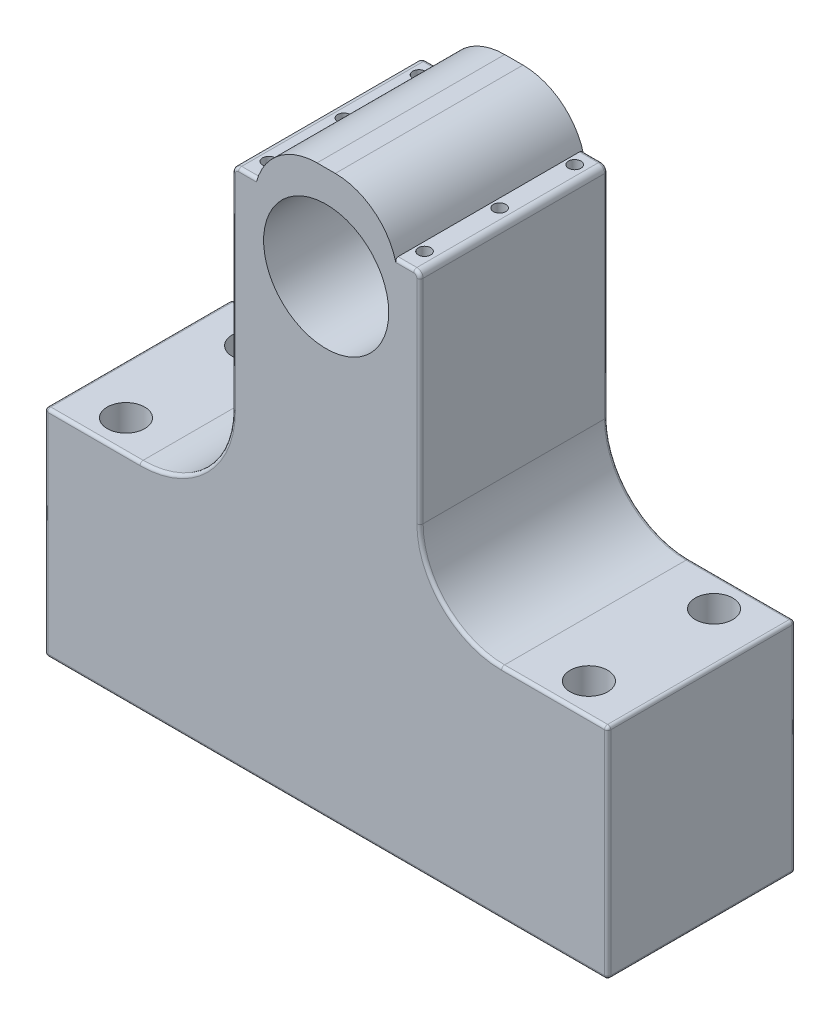
SolidWorks part; units mm, degrees
ref_plane "Plan de face" through (0, 0, 0) normal (0, 0, 1) x (1, 0, 0)
ref_plane "Plan de dessus" through (0, 0, 0) normal (0, 1, 0) x (1, 0, 0)
ref_plane "Plan de droite" through (0, 0, 0) normal (1, 0, 0) x (0, 0, -1)
sketch "Esquisse1" plane through (0, 0, 0) normal (0, 0, 1) x (1, 0, 0)
  line L0 (0, 0) -> (900, 0)
  line L1 (900, 0) -> (900, 150)
  line L3 (0, 144.3329) -> (0, 0)
  line L4 (300, 374.9177) -> (300, 630)
  line L5 (340, 700) -> (560, 700)
  line L6 (600, 630) -> (600, 375)
  line L7 (0, 144.3329) -> (152.4789, 144.3329)
  line L8 (300, 291.854) -> (300, 374.9177)
  line L9 (900, 150) -> (730.278, 150)
  line L10 (600, 375) -> (600, 280.278)
  line L11 (560, 700) -> (560, 630)
  line L12 (560, 630) -> (600, 630)
  line L16 (300, 630) -> (340, 630)
  line L17 (340, 700) -> (340, 630)
  circle A2 centre (450, 550) radius 100
  arc A3 (152.4789, 144.3329) -> (300, 291.854) centre (152.4789, 291.854) ccw
  arc A4 (730.278, 150) -> (600, 280.278) centre (730.278, 280.278) cw
  point P6 (320, 630)
  dimension "D1" = 200
  dimension "D2" = 550
  dimension "D3" = 40
  dimension "D4" = 700
  dimension "D5" = 40
  dimension "D6" = 300
  dimension "D7" = 900
  dimension "D8" = 450
  dimension "D9" = 70
  dimension "D10" = 70
extrude "Boss.-Extru.1" add sketch "Esquisse1" against normal blind 300
sketch "Esquisse2" plane through (0, 144.3329, 0) normal (0, 1, 0) x (1, 0, 0)
  line L0 (152.4789, 300) -> (0, 300) construction
  line L1 (152.4789, 0) -> (0, 0) construction
  line L2 (0, 300) -> (0, 0) construction
  circle A0 centre (80, 250) radius 30
  circle A1 centre (80, 50) radius 30
  dimension "D1" = 60
  dimension "D2" = 60
  dimension "D3" = 50
  dimension "D4" = 50
  dimension "D5" = 80
  dimension "D6" = 80
extrude "Enlèv. mat.-Extru.1" cut sketch "Esquisse2" against normal blind 500
fillet "Congé3" radius 100 2 edges at (340, 700, -150) (560, 700, -150)
fillet "Congé4" radius 10 2 edges at (300, 630, -150) (600, 630, -150)
sketch "Esquisse3" plane through (0, 150, 0) normal (0, 1, 0) x (1, 0, 0)
  line L0 (900, 300) -> (730.278, 300) construction
  line L1 (900, 0) -> (730.278, 0) construction
  line L2 (900, 300) -> (900, 0) construction
  circle A0 centre (820, 250) radius 30
  circle A1 centre (820, 50) radius 30
  dimension "D1" = 60
  dimension "D2" = 60
  dimension "D3" = 50
  dimension "D4" = 50
  dimension "D5" = 80
  dimension "D6" = 80
extrude "Enlèv. mat.-Extru.2" cut sketch "Esquisse3" against normal blind 500
sketch "Esquisse4" plane through (0, 630, 0) normal (0, 1, 0) x (1, 0, 0)
  circle A0 centre (573.7843, 273.4522) radius 10
  circle A1 centre (324.8854, 273.4522) radius 10
  dimension "D1" = 20
  dimension "D2" = 20
extrude "Enlèv. mat.-Extru.3" cut sketch "Esquisse4" against normal blind 100
pattern_linear "Répétition linéaire1" count 3 spacing 120 along (0, 0, 1) of "Enlèv. mat.-Extru.3"
sketch "Esquisse6" plane through (0, 0, 0) normal (0, 0, 1) x (1, 0, 0)
  line L0 (0, 0) -> (0, -200)
  line L1 (0, -200) -> (900, -200)
  line L2 (900, -200) -> (900, 0)
  line L3 (0, 0) -> (900, 0) construction
  line L4 (0, 0) -> (900, 0)
  point P3 (900, -140.103)
  dimension "D1" = 200
extrude "Boss.-Extru.2" add sketch "Esquisse6" against normal blind 300
sketch "Esquisse7" plane through (0, 0, 0) normal (0, 1, 0) x (1, 0, 0)
  circle A0 centre (80.6625, 253.0556) radius 33.1266
  circle A1 centre (80, 50) radius 30
  circle A2 centre (816.2966, 50) radius 26.2966
  circle A3 centre (820, 250) radius 30
extrude "Enlèv. mat.-Extru.4" cut sketch "Esquisse7" against normal blind 300
fillet "Congé6" radius 5 30 edges at (815.139, 150, 0) (575, 630, 0) (597.0711, 627.0711, 0) (600, 450.139, 0) (815.139, 150, -300) (575, 630, -300) (597.0711, 627.0711, -300) (600, 450.139, -300) (325, 630, -300) (302.9289, 627.0711, -300) (300, 455.927, -300) (256.7921, 187.5409, -300) (325, 630, 0) (302.9289, 627.0711, 0) (76.2395, 144.3329, 0) (256.7921, 187.5409, 0) (900, -200, -150) (450, -200, -300) (0, -200, -150) (450, -200, 0) (638.1576, 188.1576, 0) (900, 150, -150) (900, -25, 0) (900, -25, -300) (638.1576, 188.1576, -300) (76.2395, 144.3329, -300) (0, -27.8335, -300) (0, 144.3329, -150) (0, -27.8335, 0) (300, 455.927, 0)
